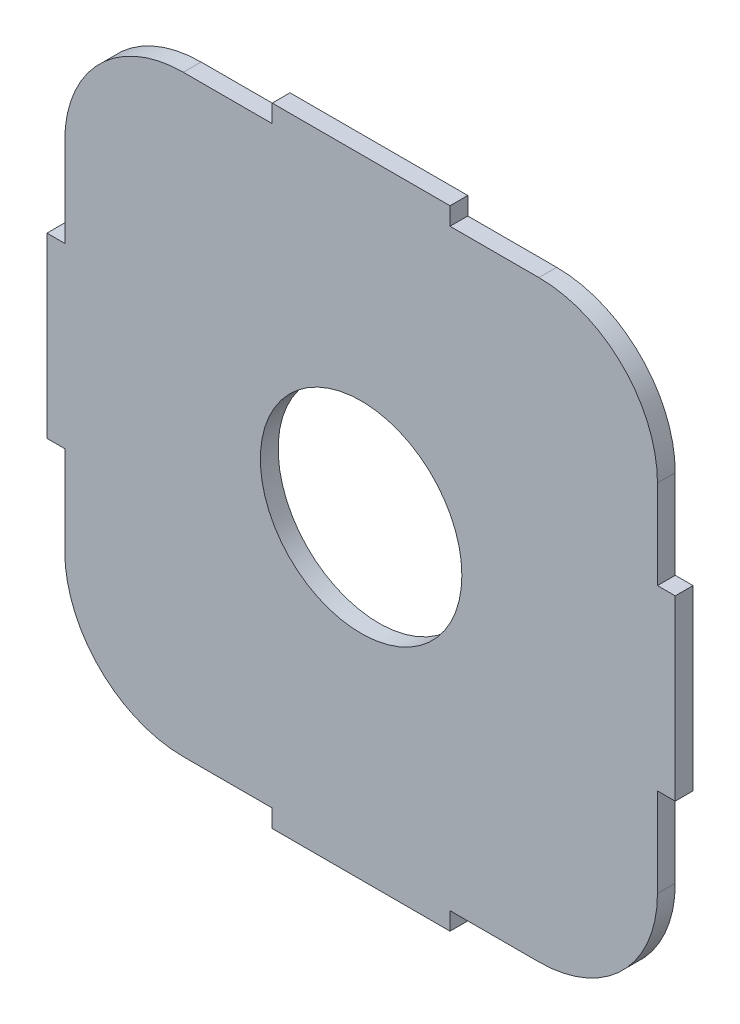
SolidWorks part; units mm, degrees
ref_plane "Plan de face" through (0, 0, 0) normal (0, 0, 1) x (1, 0, 0)
ref_plane "Plan de dessus" through (0, 0, 0) normal (0, 1, 0) x (1, 0, 0)
ref_plane "Plan de droite" through (0, 0, 0) normal (1, 0, 0) x (0, 0, -1)
sketch "Esquisse1" plane through (0, 0, 0) normal (0, 0, 1) x (1, 0, 0)
  line L0 (0, 0) -> (0, 35)
  line L1 (0, 100) -> (35, 100)
  line L2 (100, 100) -> (100, 65)
  line L3 (100, 0) -> (65, 0)
  line L4 (-3, 35) -> (-3, 65)
  line L5 (-3, 65) -> (0, 65)
  line L6 (-3, 35) -> (0, 35)
  line L7 (35, 103) -> (65, 103)
  line L8 (65, 103) -> (65, 100)
  line L9 (35, 103) -> (35, 100)
  line L10 (103, 65) -> (103, 35)
  line L11 (103, 35) -> (100, 35)
  line L12 (103, 65) -> (100, 65)
  line L13 (65, -3) -> (35, -3)
  line L14 (35, -3) -> (35, 0)
  line L15 (65, -3) -> (65, 0)
  line L16 (65, 100) -> (100, 100)
  line L17 (100, 35) -> (100, 0)
  line L18 (35, 0) -> (0, 0)
  line L19 (0, 65) -> (0, 100)
  point P8 (-3, 50)
  point P25 (50, 50)
  dimension "D1" = 100
  dimension "D3" = 3
  dimension "D4" = 30
  dimension "D5" = 4
extrude "Boss.-Extru.1" add sketch "Esquisse1" along normal blind 3
sketch "Esquisse3" plane through (0, 0, 3) normal (0, 0, 1) x (1, 0, 0)
  line L0 (100, 100) -> (0, 0) construction
  line L1 (0, 100) -> (100, 0) construction
sketch "Esquisse2" plane through (0, 0, 3) normal (0, 0, 1) x (1, 0, 0)
  line L0 (100, 100) -> (0, 0) construction
  circle A0 centre (50, 50) radius 17
  dimension "D1" = 34
extrude "Enlèv. mat.-Extru.1" cut sketch "Esquisse2" against normal up to surface (3 mm away) up to face at (50, 50, 0)
fillet "Congé1" radius 20 4 edges at (0, 0, 1.5) (100, 0, 1.5) (100, 100, 1.5) (0, 100, 1.5)
